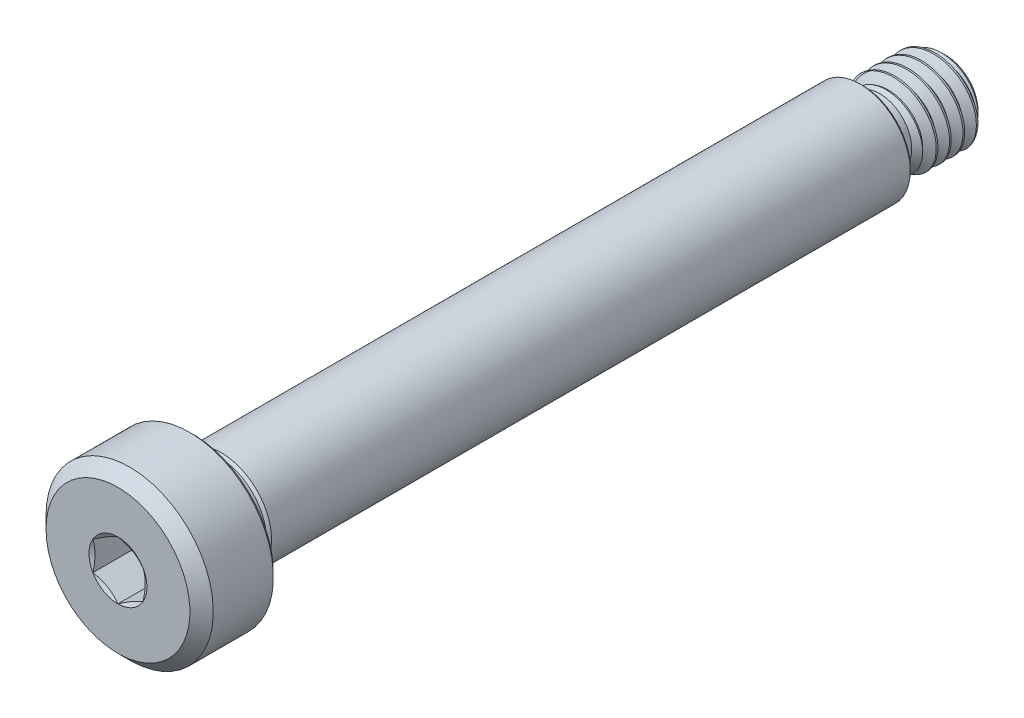
SolidWorks part; units mm, degrees
material "1023 Carbon Steel Sheet (SS)"
ref_plane "Front Plane" through (0, 0, 0) normal (0, 0, 1) x (1, 0, 0)
ref_plane "Top Plane" through (0, 0, 0) normal (0, 1, 0) x (1, 0, 0)
ref_plane "Right Plane" through (0, 0, 0) normal (1, 0, 0) x (0, 0, -1)
sketch "Sketch1" plane through (0, 0, 0) normal (0, 0, 1) x (1, 0, 0)
  line L1 (0, 1.7321) -> (-1.5, 0.866)
  line L2 (-1.5, 0.866) -> (-1.5, -0.866)
  line L3 (-1.5, -0.866) -> (0, -1.7321)
  line L4 (0, -1.7321) -> (1.5, -0.866)
  line L5 (1.5, -0.866) -> (1.5, 0.866)
  line L6 (1.5, 0.866) -> (0, 1.7321)
  circle A0 centre (0, 0) radius 5
  circle A1 centre (0, 0) radius 1.5 construction
  point P3 (0, 5)
  point P11 (0, -5)
  dimension "Head Diameter" = 10
  dimension "Drive Size" = 3
sketch "Sketch2" plane through (0, 0, 0) normal (1, 0, 0) x (0, 0, -1)
  line L0 (-24.75, 0) -> (24.75, 0) construction
  point P2 (0, 0)
  point P4 (-20.25, 0)
  point P5 (19.75, 0)
  point P6 (-20.25, -5)
  point P7 (-20.25, 5)
  point P9 (19.75, 5)
  dimension "Head Height" = 4.5
  dimension "Thread Length" = 5
  dimension "Shoulder Length" = 40
sketch "Sketch3" plane through (0, 0, 0) normal (1, 0, 0) x (0, 0, -1)
  line L0 (-24.75, 0) -> (-24.75, 5)
  line L1 (-24.75, 5) -> (-20.25, 5)
  line L2 (-20.25, 5) -> (-20.25, 0)
  line L3 (-24.75, 0) -> (-20.25, 0) construction
  line L4 (-24.75, 4.3) -> (-24.05, 5)
  line L5 (-20.46, 5) -> (-20.25, 4.79)
  point P4 (-22.275, 0)
  point P10 (-20.505, 5)
  point P11 (-24.005, 5)
  dimension "D1" = 45
  dimension "D2" = 0.045
  dimension "D3" = 0.045
  dimension "D4" = 2.475
  dimension "D5" = 0.7
  dimension "D6" = 0.21
sketch "Sketch4" plane through (0, 0, 0) normal (1, 0, 0) x (0, 0, -1)
  line L0 (-20.25, 2.85) -> (-18.72, 2.85)
  line L1 (-20.25, 5) -> (-20.25, 0) construction
  line L2 (-18.72, 2.85) -> (-18.57, 3)
  line L3 (-18.57, 3) -> (19.6, 3)
  line L4 (-18.57, 3) -> (-18.57, 0)
  line L5 (-24.75, 0) -> (24.75, 0) construction
  line L6 (-20.25, 0) -> (-18.57, 0) construction
  line L7 (19.6, 3) -> (19.75, 2.85)
  line L8 (19.75, 2.85) -> (19.75, 0)
  line L9 (-18.57, 0) -> (19.75, 0) construction
  dimension "D1" = 45
  dimension "Head Undercut Width (J)" = 1.68
  dimension "Shoulder Diameter" = 6
  dimension "D2" = 5.7
sketch "Sketch5" plane through (0, 0, 0) normal (1, 0, 0) x (0, 0, -1)
  line L0 (19.75, 0) -> (24.75, 0) construction
  line L1 (24.75, 0) -> (24.75, 2.5)
  line L2 (24.75, 2.5) -> (21.39, 2.5)
  line L3 (21.39, 2.5) -> (20.79, 1.9)
  line L4 (20.79, 1.9) -> (19.75, 1.9)
  line L5 (19.75, 2.85) -> (19.75, 0) construction
  line L6 (24.15, 2.5) -> (24.75, 1.9)
  point P4 (23.95, 0)
  point P13 (23.55, 2.5)
  point P16 (23.55, -2.5)
  point P21 (24.75, -2.5)
  point P22 (24.75, 2.5)
  dimension "Thread Diameter" = 5
  dimension "Thread Pitch" = 0.8
  dimension "D1" = 45
  dimension "D2" = 0.6
  dimension "Thread Undercut Width (M)" = 1.04
  dimension "D3" = 1.2
sketch "Sketch6" plane through (0, 0, 0) normal (1, 0, 0) x (0, 0, -1)
  line L0 (-24.75, 0) -> (-24.75, 4.3)
  line L1 (-24.75, 4.3) -> (-24.05, 5)
  line L2 (-24.05, 5) -> (-20.46, 5)
  line L3 (-20.25, 4.79) -> (-20.25, 3.15)
  line L4 (-19.95, 2.85) -> (-18.72, 2.85)
  line L5 (-18.72, 2.85) -> (-18.57, 3)
  line L6 (-18.57, 3) -> (19.6, 3)
  line L7 (19.6, 3) -> (19.75, 2.85)
  line L8 (19.75, 2.85) -> (19.75, 2.2)
  line L9 (20.05, 1.9) -> (20.79, 1.9)
  line L10 (20.79, 1.9) -> (21.39, 2.5)
  line L11 (21.39, 2.5) -> (24.15, 2.5)
  line L12 (24.15, 2.5) -> (24.75, 1.9)
  line L13 (24.75, 1.9) -> (24.75, 0)
  line L14 (24.75, 0) -> (-24.75, 0)
  line L15 (-20.46, 5) -> (-20.25, 4.79) construction
  line L16 (-20.46, 5) -> (-20.25, 4.79)
  line L17 (-19.95, 3.15) -> (-19.95, 2.85) construction
  line L18 (20.05, 1.9) -> (20.05, 2.5) construction
  arc A0 (-20.25, 3.15) -> (-19.95, 2.85) centre (-19.95, 3.15) ccw
  arc A1 (19.75, 2.2) -> (20.05, 1.9) centre (20.05, 2.2) ccw
  point P34 (-19.95, 3)
  point P37 (20.05, 2.2)
revolve "Revolve1" add sketch "Sketch6" angle 360 about L14
sketch "Sketch7" plane through (0, 0, 24.75) normal (0, 0, 1) x (1, 0, 0)
  line L0 (0, -1.7321) -> (1.5, -0.866) construction
  line L1 (-1.5, -0.866) -> (0, -1.7321) construction
  line L2 (-1.5, 0.866) -> (-1.5, -0.866) construction
  line L3 (0, 1.7321) -> (-1.5, 0.866) construction
  line L4 (1.5, 0.866) -> (0, 1.7321) construction
  line L5 (1.5, -0.866) -> (1.5, 0.866) construction
  line L6 (0, -1.7321) -> (1.5, -0.866)
  line L7 (-1.5, -0.866) -> (0, -1.7321)
  line L8 (-1.5, 0.866) -> (-1.5, -0.866)
  line L9 (0, 1.7321) -> (-1.5, 0.866)
  line L10 (1.5, 0.866) -> (0, 1.7321)
  line L11 (1.5, -0.866) -> (1.5, 0.866)
extrude "Cut-Extrude1" cut sketch "Sketch7" against normal up to vertex (2.475 mm away) up to point (0, 0, 22.275)
sketch "Sketch8" plane through (0, 0, 24.75) normal (0, 0, 1) x (1, 0, 0)
  circle A0 centre (0, 0) radius 1.7321
extrude "Cut-Extrude2" cut sketch "Sketch8" against normal up to vertex (2.475 mm away) draft 60 up to point (0, 0, 22.275)
ref_plane "Plane1" through (0, 0, -20.79) normal (0, 0, 1) x (1, 0, 0)
split "Split1" trim tools "Plane1" bodies to split 106 resulting bodies 107 108
sketch "Sketch10" plane through (0, 0, -24.75) normal (0, 0, -1) x (-1, 0, 0)
  circle A0 centre (0, 0) radius 2.5 construction
  circle A1 centre (0, 0) radius 2.5
curve "Helix/Spiral1" pitch 0.8 height 5.8 radius 2.5 centre (0, 0, -24.75) axis (0, 0, 1) start towards (0, 1, 0)
sketch "Sketch11" plane through (0, 0, 0) normal (1, 0, 0) x (0, 0, -1)
  line L0 (24.7, 2.5866) -> (25.1, 1.8938) construction
  line L1 (25.1, 1.8938) -> (25.5, 2.5866) construction
  line L2 (25.5, 2.5866) -> (24.7, 2.5866) construction
  line L3 (24.725, 2.5433) -> (25.475, 2.5433)
  line L4 (25.475, 2.5433) -> (25.15, 1.9804)
  line L5 (25.15, 1.9804) -> (25.05, 1.9804)
  line L6 (25.05, 1.9804) -> (24.725, 2.5433)
  line L7 (25.1, 1.9804) -> (25.1, 1.8938) construction
  line L8 (24.75, 2.5) -> (25.45, 2.5) construction
  line L9 (25.1, 2.5866) -> (25.1, 2.5) construction
  point P12 (25.1, 2.5433)
  dimension "D1" = 0.8
  dimension "D2" = 0.1
sweep "Cut-Sweep1" cut profiles "Sketch11" path "Helix/Spiral1" align with end faces yes
combine bodies "Combine1" operation type add bodies to combine 109 108
equation "\"D2@Sketch5\"=0.75*\"Thread Pitch@Sketch5\""
equation "\"D4@Helix/Spiral1\"=\"Thread Pitch@Sketch5\""
equation "\"D3@Helix/Spiral1\" = \"Thread Pitch@Sketch5\" + \"Thread Length@Sketch2\""
equation "\"D2@Sketch11\"=\"D1@Sketch11\"/8"
equation "\"D1@Sketch11\"=\"Thread Pitch@Sketch5\""
equation "\"D3@Sketch5\"=\"Thread Pitch@Sketch5\"*1.5"
equation "\"D2@Sketch3\" = .01 * \"Head Height@Sketch2\""
equation "\"D3@Sketch3\"=\"D2@Sketch3\""
equation "\"D4@Sketch3\"=0.55*\"Head Height@Sketch2\""
equation "\"D5@Sketch3\"=.07*\"Head Diameter@Sketch1\""
equation "\"D6@Sketch3\"=0.3*\"D5@Sketch3\""
equation "\"D2@Sketch4\" = 0.95 * \"Shoulder Diameter@Sketch4\""
equation "\"Head Undercut Width (J)@Sketch4\" = 0.28 * \"Shoulder Diameter@Sketch4\""
equation "\"Thread Undercut Width (M)@Sketch5\"=1.3*\"Thread Pitch@Sketch5\""
